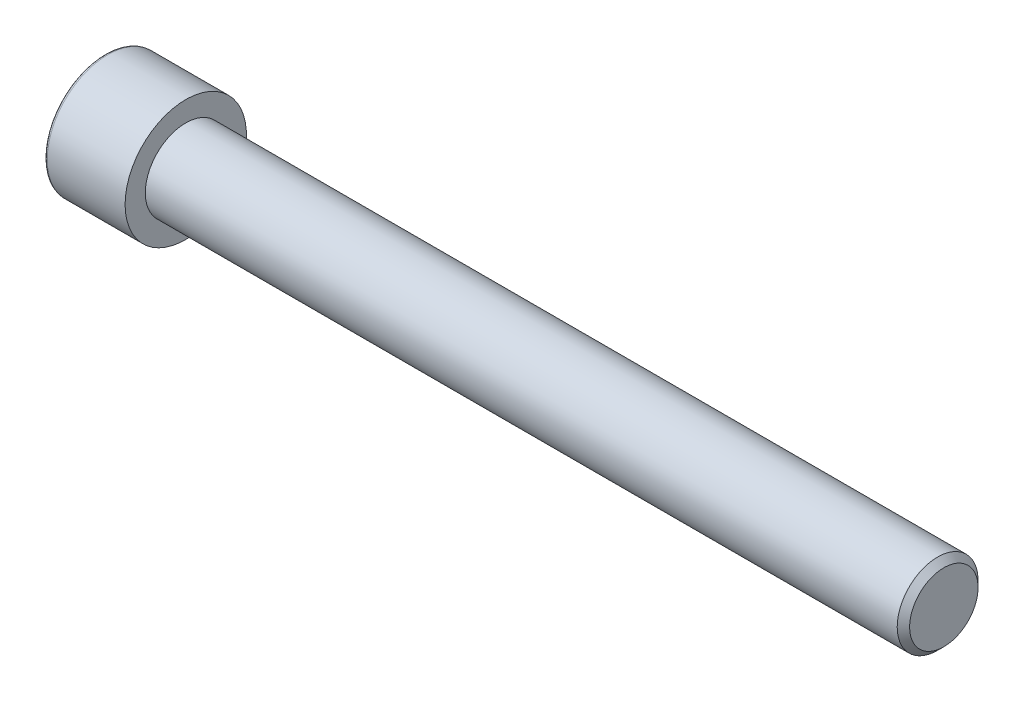
SolidWorks part; units mm, degrees
ref_plane "Płaszczyzna przednia" through (0, 0, 0) normal (0, 0, 1) x (1, 0, 0)
ref_plane "Płaszczyzna górna" through (0, 0, 0) normal (0, 1, 0) x (1, 0, 0)
ref_plane "Płaszczyzna prawa" through (0, 0, 0) normal (1, 0, 0) x (0, 0, -1)
sketch "Szkic1" plane through (0, 0, 0) normal (0, 0, 1) x (1, 0, 0)
  line L0 (0, 0) -> (0, 12)
  line L1 (0, 12) -> (16, 12)
  line L2 (16, 12) -> (16, 0)
  line L3 (16, 0) -> (0, 0)
  line L4 (16, 0) -> (0, 0) construction
revolve "Obrót1" add sketch "Szkic1" angle 360 about L4 reverse direction yes
sketch "Szkic2" plane through (0, 0, 0) normal (0, 0, 1) x (1, 0, 0)
  line L0 (0, 12) -> (0, 11.4)
  line L1 (0.6, 12) -> (0, 12)
  line L2 (16, 0) -> (0, 0) construction
  arc A0 (0, 11.4) -> (0.6, 12) centre (0.6, 11.4) cw
revolve "Wycięcie-obrót1" cut sketch "Szkic2" angle 360 about L2 reverse direction yes
sketch "Szkic3" plane through (0, 0, 0) normal (0, 0, 1) x (1, 0, 0)
  line L0 (16, 0) -> (16, 8)
  line L1 (16, 8) -> (164.773, 8)
  line L2 (164.773, 8) -> (166, 6.773)
  line L3 (166, 6.773) -> (166, 0)
  line L4 (166, 0) -> (16, 0)
  line L5 (166, 0) -> (16, 0) construction
revolve "Obrót2" add sketch "Szkic3" angle 360 about L5 reverse direction yes
cosmetic thread "Oznaczenie gwintu1" parameters "D1"=44, "D2"=13.546
cosmetic thread "Oznaczenie gwintu2" parameters "D1"=45, "D2"=13.797
sketch "Szkic4" plane through (0, 0, 0) normal (0, 0, 1) x (1, 0, 0)
  line L0 (0, 0) -> (0, 8.5)
  line L1 (0, 8.5) -> (8, 8.5)
  line L2 (8, 8.5) -> (12.9075, 0)
  line L3 (12.9075, 0) -> (0, 0)
  line L4 (12.9075, 0) -> (0, 0) construction
revolve "Wycięcie-obrót2" cut sketch "Szkic4" angle 360 about L4 reverse direction yes
sketch "Szkic5" plane through (0, 0, 0) normal (1, 0, 0) x (0, 0, -1)
  line L0 (-7, 4.0415) -> (-7, -4.0415)
  line L1 (-7, -4.0415) -> (0, -8.0829)
  line L2 (0, -8.0829) -> (7, -4.0415)
  line L3 (7, -4.0415) -> (7, 4.0415)
  line L4 (7, 4.0415) -> (0, 8.0829)
  line L5 (0, 8.0829) -> (-7, 4.0415)
  circle A0 centre (0, 0) radius 9
extrude "Dodanie-wyciągnięcie1" add sketch "Szkic5" along normal blind 12
ref_plane "Płaszczyzna1" through (16, 0, 0) normal (1, 0, 0) x (0, 0, -1)
ref_plane "IP2 XY" through (16, 0, 0) normal (-1, 0, 0) x (0, 0, 1)
ref_plane "IP2 XZ" through (0, 0, 0) normal (0, 1, 0) x (1, 0, 0)
ref_plane "IP2 YZ" through (0, 0, 0) normal (0, 0, -1) x (-1, 0, 0)
ref_axis "IP2 X" through (16, 0, 80.9) along (0, 0, -1)
ref_axis "IP2 Y" through (16, 50, 0) along (0, -1, 0)
ref_axis "IP2 Z" through (-80.9, 0, 0) along (1, 0, 0)
sketch3d "IP2"
  point P0 (16, 0, 0)
